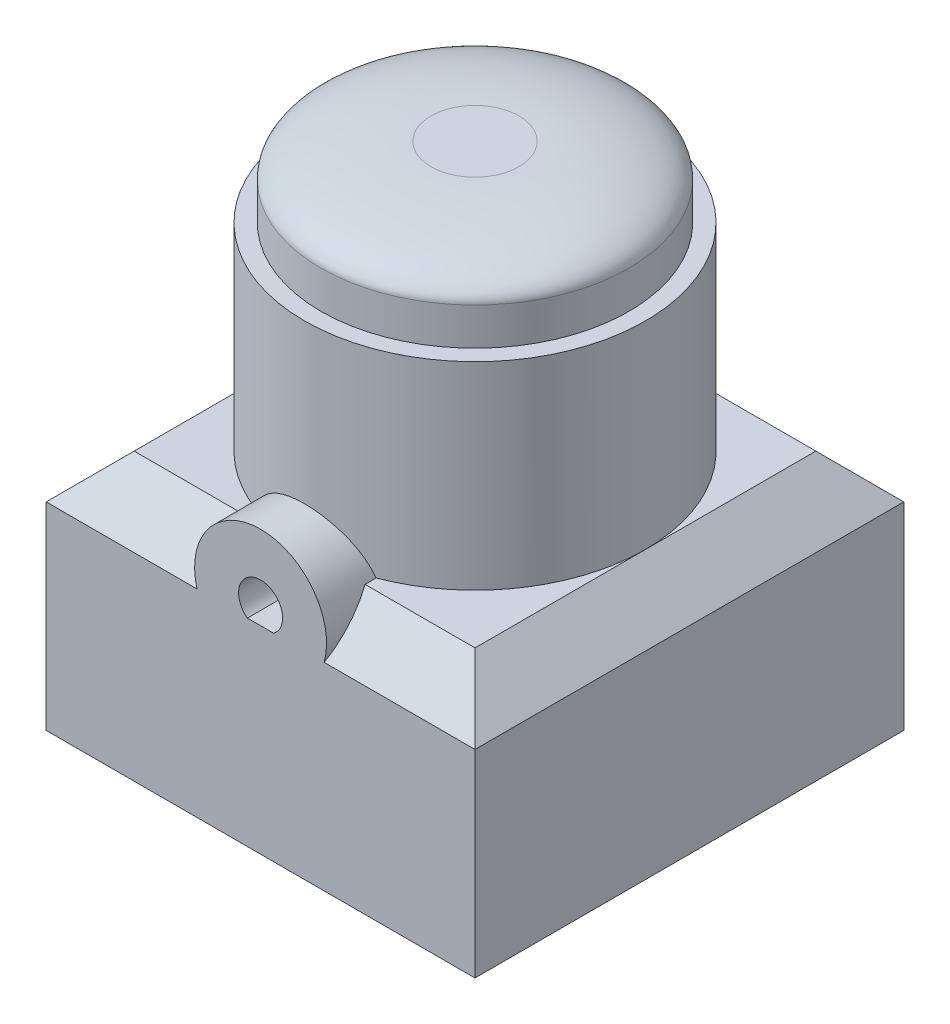
SolidWorks part; units mm, degrees
ref_plane "Front" through (0, 0, 0) normal (0, 0, 1) x (1, 0, 0)
ref_plane "Top" through (0, 0, 0) normal (0, 1, 0) x (1, 0, 0)
ref_plane "Right" through (0, 0, 0) normal (1, 0, 0) x (0, 0, -1)
sketch "Sketch1" plane through (0, 0, 0) normal (0, 1, 0) x (1, 0, 0)
  line L1 (-9.75, -9.75) -> (9.75, -9.75)
  line L2 (-9.75, -9.75) -> (-9.75, 9.75)
  line L3 (-9.75, 9.75) -> (9.75, 9.75)
  line L4 (9.75, -9.75) -> (9.75, 9.75)
  line L5 (-9.75, -9.75) -> (9.75, 9.75) construction
  line L6 (-9.75, 9.75) -> (9.75, -9.75) construction
  point P0 (0, 0)
  dimension "D1" = 19.5
extrude "Boss-Extrude1" add sketch "Sketch1" along normal blind 11
sketch "Sketch2" plane through (0, 11, 0) normal (0, 1, 0) x (1, 0, 0)
  circle A0 centre (0, 0) radius 7.75
  dimension "D1" = 15.5
extrude "Boss-Extrude2" add sketch "Sketch2" along normal blind 9
sketch "Sketch3" plane through (0, 20, 0) normal (0, 1, 0) x (1, 0, 0)
  circle A0 centre (0, 0) radius 7
  dimension "D1" = 14
extrude "Boss-Extrude3" add sketch "Sketch3" along normal blind 3.2
fillet "Fillet1" radius 1.5 1 edges at (0, 23.2, 7) second distance 5 first distance on face at (0, 23.2, 7)
chamfer "Chamfer1" distance 2 angle 45 4 edges at (9.75, 11, 0) (0, 11, -9.75) (-9.75, 11, 0) (0, 11, 9.75)
sketch "Sketch4" plane through (0, 0, 9.75) normal (0, 0, 1) x (1, 0, 0)
  line L0 (-7.75, 11) -> (0, 11) construction
  line L1 (9.75, 9) -> (-9.75, 9) construction
  line L2 (9.75, 9) -> (-9.75, 9)
  circle A0 centre (0, 9.8) radius 1
  circle A1 centre (0, 9.8) radius 3
  line M3 (9.75, 9) -> (-9.75, 9)
  dimension "D1" = 2
  dimension "D2" = 1.2
  dimension "D3" = 2
extrude "Boss-Extrude8" add sketch "Sketch4" against normal up to next contours L2 A1 A0 M3 | A1 L2 A0 M3 region at (0, 8.0699, 9.75) region at (0, 10.8043, 9.75)
sketch "Sketch5" plane through (0, 0, 9.75) normal (0, 0, 1) x (1, 0, 0)
  arc A0 (0.6, 9) -> (-0.6, 9) centre (0, 9.8) ccw construction
  arc A1 (0.6, 9) -> (-0.6, 9) centre (0, 9.8) ccw
  circle A2 centre (0, 9.8) radius 1
  line M7 (0.6, 9) -> (-0.6, 9)
  arc M8 (-0.6, 9) -> (0.6, 9) centre (0, 9.8) cw
extrude "Cut-Extrude1" cut sketch "Sketch5" against normal blind 3.2 contours M7 M8 region at (0, 9.8484, 9.75)
